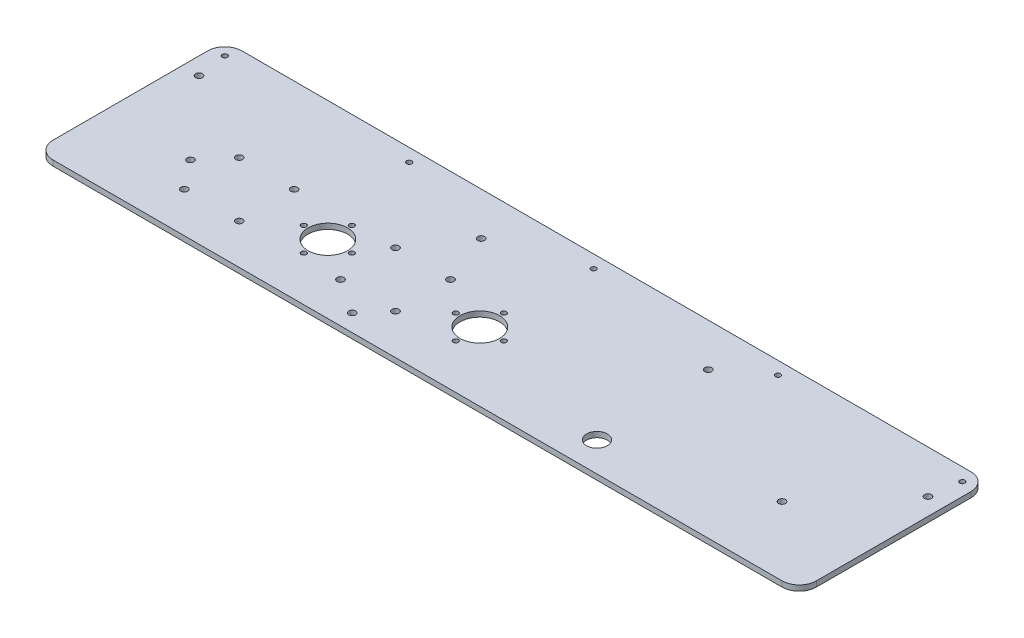
SolidWorks part; units mm, degrees
ref_plane "Front" through (0, 0, 0) normal (0, 0, 1) x (1, 0, 0)
ref_plane "Top" through (0, 0, 0) normal (0, 1, 0) x (1, 0, 0)
ref_plane "Right" through (0, 0, 0) normal (1, 0, 0) x (0, 0, -1)
sketch "Sketch1" plane through (0, 0, 0) normal (0, 1, 0) x (1, 0, 0)
  line L0 (-26.7996, 0) -> (-26.7996, 40)
  line L1 (-26.7996, 0) -> (417.7004, 0)
  line L2 (-26.7996, 0) -> (-26.7996, 110)
  line L3 (-26.7996, 110) -> (417.7004, 110)
  line L4 (417.7004, 0) -> (417.7004, 110)
  line L5 (-26.7996, 40) -> (23.2004, 40)
  line L6 (417.7004, 0) -> (417.7004, 40)
  line L7 (417.7004, 40) -> (367.7004, 40)
  line L8 (23.2004, 40) -> (103.2004, 40)
  line L9 (367.7004, 40) -> (191.7004, 40)
  line L10 (-26.7996, 110) -> (-26.7996, 85)
  line L11 (-26.7996, 85) -> (417.7004, 85)
  line L12 (-26.7996, 85) -> (-16.7996, 85)
  line L13 (417.7004, 85) -> (407.7004, 85)
  line L14 (103.2004, 40) -> (191.7004, 40)
  line L15 (147.4504, 40) -> (147.4504, 85)
  line L16 (279.7004, 40) -> (279.7004, 85)
  line L17 (147.4504, 40) -> (147.4504, 10)
  line L18 (-26.7996, 110) -> (-26.7996, 102.5)
  line L19 (-26.7996, 102.5) -> (417.7004, 102.5)
  line L20 (-26.7996, 102.5) -> (-19.2996, 102.5)
  line L21 (417.7004, 102.5) -> (410.2004, 102.5)
  line L22 (195.4504, 102.5) -> (410.2004, 102.5)
  line L23 (-19.2996, 102.5) -> (195.4504, 102.5)
  line L24 (417.7004, 0) -> (417.7004, 17.2282)
  line L25 (417.7004, 17.2282) -> (282.7004, 17.2282)
  circle A10 centre (367.7004, 40) radius 2
  circle A11 centre (23.2004, 40) radius 2
  circle A12 centre (103.2004, 40) radius 11.5
  circle A13 centre (103.2004, 40) radius 14
  circle A15 centre (103.2004, 54) radius 1.5
  circle A16 centre (89.2004, 40) radius 1.5
  circle A17 centre (103.2004, 26) radius 1.5
  circle A18 centre (117.2004, 40) radius 1.5
  circle A19 centre (191.7004, 40) radius 11.5
  circle A20 centre (191.7004, 40) radius 14
  circle A21 centre (191.7004, 26) radius 1.5
  circle A22 centre (205.7004, 40) radius 1.5
  circle A23 centre (191.7004, 54) radius 1.5
  circle A24 centre (177.7004, 40) radius 1.5
  circle A25 centre (-16.7996, 85) radius 2
  circle A26 centre (407.7004, 85) radius 2
  circle A27 centre (147.4504, 85) radius 2
  circle A28 centre (279.7004, 85) radius 2
  circle A29 centre (147.4504, 10) radius 2
  circle A30 centre (195.4504, 102.5) radius 1.5
  circle A31 centre (-19.2996, 102.5) radius 1.5
  circle A32 centre (410.2004, 102.5) radius 1.5
  circle A33 centre (302.8254, 102.5) radius 1.5
  circle A34 centre (88.0754, 102.5) radius 1.5
  circle A35 centre (282.7004, 17.2282) radius 6
  dimension "D3" = 40
  dimension "D7" = 80
  dimension "D8" = 176
  dimension "D9" = 25
  dimension "D11" = 10
  dimension "D12" = 30
  dimension "D13" = 7.5
  dimension "D14" = 7.5
  dimension "D16" = 17.2282
  dimension "D1" = 110
  dimension "D2" = 444.5
  dimension "D4" = 50
  dimension "D5" = 40
  dimension "D6" = 50
  dimension "D10" = 10
  dimension "D15" = 7.5
  dimension "D17" = 135
extrude "Boss-Extrude1" add sketch "Sketch1" along normal blind 3.175 contours A18 L14 A12 L8 A16 A13 A17 | A18 A13 A15 A16 L8 A12 L14 | A24 L14 A19 L9 A22 A20 A23 | A24 A20 A21 A22 L9 A19 L14 | A29 L14 A18 A13 A17 A16 L8 A11 L5 L0 L1 L4 L7 A10 L9 A22 A20 A21 A24 | A28 L11 A27 L15 L14 A24 A20 A23 A22 L9 L16 | A27 L11 A25 L2 L5 A11 L8 A16 A13 A15 A18 L14 L15 | A28 L11 A26 L13 L4 L3 L2 A25 A27 | A28 L16 L9 A10 L7 L4 L13 A26 L11 | A34 L23 A30 L22 A33 A32 L21 L4 L3 L10 L19 A31 region at (196.684, 0, -19.4923) region at (58.5861, 0, -63.184) region at (195.421, 0, -93.7571) region at (195.4504, 0, -106.2666) region at (348.6559, 0, -62.489) region at (93.521, 0, -49.6794) region at (90.515, 0, -38.754) region at (214.7998, 0, -63.4004) region at (204.3858, 0, -41.246) region at (201.3798, 0, -30.3206)
fillet "Fillet1" radius 10 4 edges at (417.7004, 1.5875, -110) (417.7004, 1.5875, 0) (-26.7996, 1.5875, 0) (-26.7996, 1.5875, -110)
sketch "Sketch2" plane through (0, 3.175, 0) normal (0, 1, 0) x (1, 0, 0)
  line L0 (-26.7996, 55.4056) -> (36.2004, 55.4056)
  line L1 (-26.7996, 10) -> (-26.7996, 100) construction
  line L2 (36.2004, 55.4056) -> (68.2004, 55.4056)
  line L3 (-16.7996, 110) -> (407.7004, 110) construction
  line L4 (36.2004, 55.4056) -> (36.2004, 23.4056)
  line L5 (36.2004, 23.4056) -> (68.2004, 23.4056)
  line L6 (68.2004, 55.4056) -> (159.2004, 55.4056)
  line L7 (159.2004, 55.4056) -> (127.2004, 55.4056)
  circle A0 centre (36.2004, 55.4056) radius 2
  circle A1 centre (68.2004, 55.4056) radius 2
  circle A2 centre (36.2004, 23.4056) radius 2
  circle A3 centre (68.2004, 23.4056) radius 2
  circle A4 centre (127.2004, 55.4056) radius 2
  circle A5 centre (159.2004, 55.4056) radius 2
  circle A7 centre (159.2004, 23.4056) radius 2
  circle A8 centre (127.2004, 23.4056) radius 2
  dimension "D5" = 91
  dimension "D6" = 32
  dimension "D1" = 63
  dimension "D2" = 32
  dimension "D3" = 54.5944
  dimension "D4" = 32
extrude "Cut-Extrude1" cut sketch "Sketch2" against normal blind 10 contours A0 | A1 | A2 | A3 | A4 | A8 | A7 | A5
